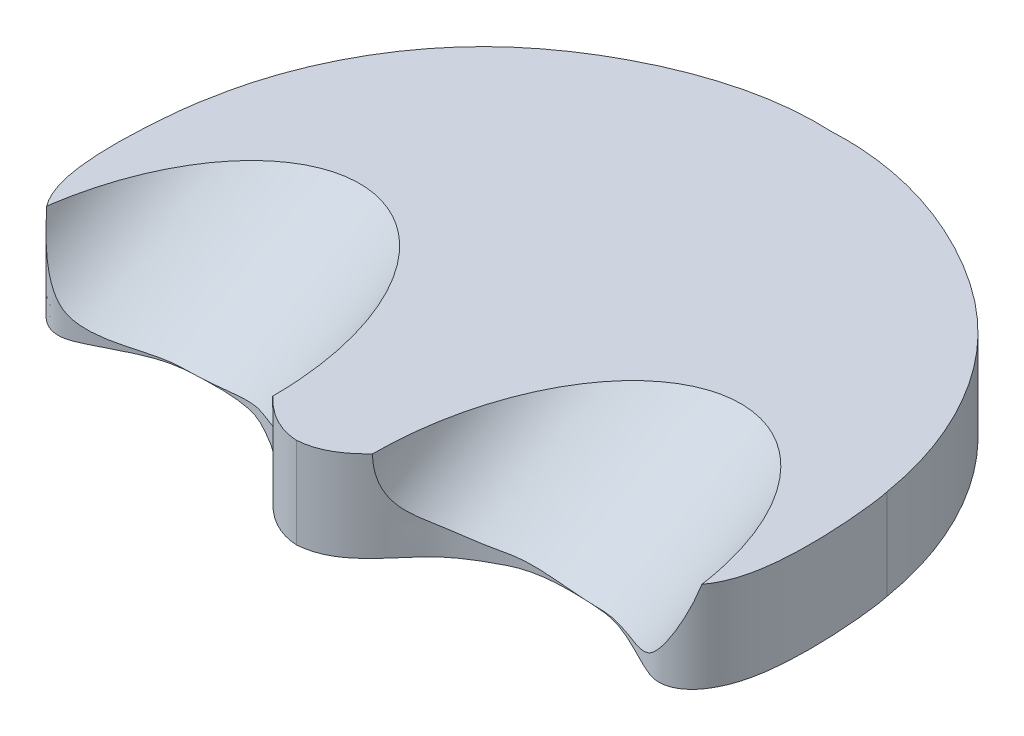
SolidWorks part; units mm, degrees
material "6061-T6 (SS)"
ref_plane "Front Plane" through (0, 0, 0) normal (0, 0, 1) x (1, 0, 0)
ref_plane "Top Plane" through (0, 0, 0) normal (0, 1, 0) x (1, 0, 0)
ref_plane "Right Plane" through (0, 0, 0) normal (1, 0, 0) x (0, 0, -1)
sketch "Sketch3" plane through (0, 0, 0) normal (0, 1, 0) x (1, 0, 0)
  line L0 (0, 0) -> (0, 159.1899) construction
  line L1 (0, 0) -> (0, -140.5301) construction
  line L2 (0, 0) -> (-190.5, 0) construction
  line L3 (0, 0) -> (190.5, 0) construction
  spline S0 degree 3 poles (-190.5, 0) (-184.3927, 37.537) (-157.2613, 93.9641) (-82.3875, 146.6227) (-31.3114, 160.7999) (0, 159.1899) knots 0 0 0 0 0.424401 0.65637 1 1 1 1
  spline S1 degree 3 poles (-190.5, 0) (-192.064, -4.9635) (-201.9672, -83.3146) (-174.6966, -109.29) (-151.6301, -100.568) (-131.4108, -87.7198) (-96.8436, -85.3754) (-78.6925, -86.2588) (-58.8335, -96.8794) (-37.3059, -109.9358) (-21.3496, -139.1148) (0, -140.5301) knots 0 0 0 0 0.166997 0.292321 0.319633 0.426735 0.458914 0.609242 0.64191 0.766802 1 1 1 1
  spline S2 degree 3 poles (190.5, 0) (192.064, -4.9635) (201.9672, -83.3146) (174.6966, -109.29) (151.6301, -100.568) (131.4108, -87.7198) (96.8436, -85.3754) (78.6925, -86.2588) (58.8335, -96.8794) (37.3059, -109.9358) (21.3496, -139.1148) (0, -140.5301) knots 0 0 0 0 0.166997 0.292321 0.319633 0.426735 0.458914 0.609242 0.64191 0.766802 1 1 1 1
  spline S3 degree 3 poles (190.5, 0) (184.3927, 37.537) (157.2613, 93.9641) (82.3875, 146.6227) (31.3114, 160.7999) (0, 159.1899) knots 0 0 0 0 0.424401 0.65637 1 1 1 1
  dimension "D1" = 381
  dimension "D2" = 299.72
  dimension "D3" = 159.1899
  dimension "D4" = 86.8953
  dimension "D5" = 104.4979
  dimension "D6" = 29.1616
  dimension "D7" = 92.2742
  dimension "D8" = 108.411
  dimension "D9" = 67.4883
  dimension "D10" = 43.7314
  dimension "D11" = 117.6915
  dimension "D12" = 162.2568
  dimension "D13" = 89.4522
  dimension "D14" = 140.1036
  dimension "D15" = 175.0666
  dimension "D16" = 50.2669
  dimension "D17" = 101.3666
  dimension "D18" = 138.1225
  dimension "D19" = 155.1557
  dimension "D20" = 192.0074
  dimension "D21" = 193.9268
  dimension "D23" = 76.6666
extrude "Boss-Extrude1" add sketch "Sketch3" along normal blind 50.8 from surface starting at plane "Top Plane"
sketch "Sketch5" plane through (0, 0, 0) normal (0, -1, 0) x (1, 0, 0)
  line L0 (0, 0) -> (0, -20.32) construction
  line L1 (31.75, -52.07) -> (-31.75, -52.07)
  line L2 (31.75, -52.07) -> (31.75, 11.43)
  line L3 (31.75, 11.43) -> (-31.75, 11.43)
  line L4 (-31.75, -52.07) -> (-31.75, 11.43)
  line L5 (31.75, -52.07) -> (-31.75, 11.43) construction
  line L6 (31.75, 11.43) -> (-31.75, -52.07) construction
  line L7 (-31.75, -52.07) -> (-31.75, -30.48)
  line L8 (-31.75, -30.48) -> (31.75, -30.48) construction
  line L9 (0, -20.32) -> (140.7253, -20.32) construction
  line L10 (0, -20.32) -> (0, -97.1287) construction
  line L11 (0, -20.32) -> (31.9753, -118.7297) construction
  line L13 (0, -20.32) -> (63.8443, -108.1942) construction
  line L14 (0, -20.32) -> (95.5392, -89.7333) construction
  line L15 (124.7166, -60.8429) -> (0, -20.32) construction
  line L16 (0, -20.32) -> (154.5508, 21.0918) construction
  line L17 (0, -20.32) -> (148.922, 65.6601) construction
  line L18 (0, -20.32) -> (-31.9753, -118.7297) construction
  line L19 (0, -20.32) -> (-63.8443, -108.1942) construction
  line L20 (0, -20.32) -> (-95.5392, -89.7333) construction
  line L21 (-124.7166, -60.8429) -> (0, -20.32) construction
  line L22 (0, -20.32) -> (-154.5508, 21.0918) construction
  line L23 (0, -20.32) -> (-148.922, 65.6601) construction
  spline S0 degree 3 poles (-148.922, 65.6601) (-157.8584, 40.2253) (-156.2837, 8.5854) (-143.1202, -28.9506) (-139.3242, -37.3463) (-130.3709, -53.1962) (-125.215, -60.649) (-118.0488, -69.1403) (-116.5795, -70.7975) (-113.5719, -74.0252) (-112.0368, -75.592) (-107.2801, -80.2116) (-103.9215, -83.1695) (-93.3361, -91.6595) (-85.5959, -96.8074) (-76.3408, -101.9556) (-75.3049, -102.5187) (-73.219, -103.6268) (-72.1677, -104.1726) (-69.0049, -105.7765) (-66.8862, -106.8006) (-60.5068, -109.7299) (-56.2231, -111.4921) (-47.6308, -114.6027) (-43.3223, -115.9511) (-34.7104, -118.209) (-30.4072, -119.1185) (-21.8242, -120.4791) (-17.5446, -120.9304) (-11.1443, -121.2499) (-9.0138, -121.2968) (-5.8216, -121.2757) (-4.1848, -121.2414) (-2.5489, -121.1705) (-1.9677, -121.1408) (-1.9605, -121.1404) (-1.2995, -121.1064) (-0.6497, -121.073) (0, -121.0396) knots -0.292878 -0.292878 -0.292878 -0.292878 0.125 0.125 0.25 0.25 0.375 0.375 0.40625 0.40625 0.4375 0.4375 0.5 0.5 0.625 0.625 0.640625 0.640625 0.65625 0.65625 0.6875 0.6875 0.75 0.75 0.8125 0.8125 0.875 0.875 0.9375 0.9375 0.96875 0.96875 0.984375 0.992798 0.992798 0.99292 0.99292 1 1 1 1
  spline S5 degree 3 poles (998.6789, -69.6893) (665.1581, -86.8384) (331.6156, -103.9885) (-1.9268, -121.1387) (-1.9605, -121.1404) (-1.9677, -121.1408) (-2.5489, -121.1705) (-4.1848, -121.2414) (-5.8216, -121.2757) (-9.0138, -121.2968) (-11.1443, -121.2499) (-17.5446, -120.9304) (-21.8242, -120.4791) (-30.4072, -119.1185) (-34.7104, -118.209) (-43.3223, -115.9511) (-47.6308, -114.6027) (-56.2231, -111.4921) (-60.5068, -109.7299) (-66.8862, -106.8006) (-69.0049, -105.7765) (-72.1677, -104.1726) (-73.219, -103.6268) (-75.3049, -102.5187) (-76.3408, -101.9556) (-85.5959, -96.8074) (-93.3361, -91.6595) (-103.9215, -83.1695) (-107.2801, -80.2116) (-112.0368, -75.592) (-113.5719, -74.0252) (-116.5795, -70.7975) (-118.0488, -69.1403) (-125.215, -60.649) (-130.3709, -53.1962) (-139.3242, -37.3463) (-143.1202, -28.9506) (-198.5095, 128.9933) (-22.362, 351.6373) (651.8169, -587.5188) knots -3.627409 -3.627409 -3.627409 -3.627409 0.006836 0.00708 0.00708 0.007202 0.007202 0.015625 0.03125 0.03125 0.0625 0.0625 0.125 0.125 0.1875 0.1875 0.25 0.25 0.3125 0.3125 0.34375 0.34375 0.359375 0.359375 0.375 0.375 0.5 0.5 0.5625 0.5625 0.59375 0.59375 0.625 0.625 0.75 0.75 0.875 0.875 3.034324 3.034324 3.034324 3.034324 only from (0, -121.0396) to (-152.8945, 6.1184)
  spline S6 degree 3 poles (-1687.8289, -2297.0686) (-150.4269, 537.0593) (218.9922, 187.4002) (143.1202, -28.9506) (139.3242, -37.3463) (130.3709, -53.1962) (125.215, -60.649) (118.0488, -69.1403) (116.5795, -70.7975) (113.5719, -74.0252) (112.0368, -75.592) (107.2801, -80.2116) (103.9215, -83.1695) (93.3361, -91.6595) (85.5959, -96.8074) (76.3408, -101.9556) (75.3049, -102.5187) (73.219, -103.6268) (72.1677, -104.1726) (69.0049, -105.7765) (66.8862, -106.8006) (60.5068, -109.7299) (56.2231, -111.4921) (47.6308, -114.6027) (43.3223, -115.9511) (34.7104, -118.209) (30.4072, -119.1185) (21.8242, -120.4791) (17.5446, -120.9304) (11.1443, -121.2499) (9.0138, -121.2968) (5.8216, -121.2757) (4.1848, -121.2414) (2.5489, -121.1705) (1.9677, -121.1408) (1.9605, -121.1404) (-997.3522, -69.7575) (-1996.6535, -18.3753) (-2996.029, 33.0152) knots -2.879056 -2.879056 -2.879056 -2.879056 0.125 0.125 0.25 0.25 0.375 0.375 0.40625 0.40625 0.4375 0.4375 0.5 0.5 0.625 0.625 0.640625 0.640625 0.65625 0.65625 0.6875 0.6875 0.75 0.75 0.8125 0.8125 0.875 0.875 0.9375 0.9375 0.96875 0.96875 0.984375 0.992798 0.992798 0.99292 0.99292 11.881939 11.881939 11.881939 11.881939 only from (152.8945, 6.1184) to (0, -121.0396)
  spline S8 degree 3 poles (148.922, 65.6601) (157.8584, 40.2253) (156.2837, 8.5854) (143.1202, -28.9506) (139.3242, -37.3463) (130.3709, -53.1962) (125.215, -60.649) (118.0488, -69.1403) (116.5795, -70.7975) (113.5719, -74.0252) (112.0368, -75.592) (107.2801, -80.2116) (103.9215, -83.1695) (93.3361, -91.6595) (85.5959, -96.8074) (76.3408, -101.9556) (75.3049, -102.5187) (73.219, -103.6268) (72.1677, -104.1726) (69.0049, -105.7765) (66.8862, -106.8006) (60.5068, -109.7299) (56.2231, -111.4921) (47.6308, -114.6027) (43.3223, -115.9511) (34.7104, -118.209) (30.4072, -119.1185) (21.8242, -120.4791) (17.5446, -120.9304) (11.1443, -121.2499) (9.0138, -121.2968) (5.8216, -121.2757) (4.1848, -121.2414) (2.5489, -121.1705) (1.9677, -121.1408) (1.9605, -121.1404) (1.2995, -121.1064) (0.6497, -121.073) (0, -121.0396) knots -0.292878 -0.292878 -0.292878 -0.292878 0.125 0.125 0.25 0.25 0.375 0.375 0.40625 0.40625 0.4375 0.4375 0.5 0.5 0.625 0.625 0.640625 0.640625 0.65625 0.65625 0.6875 0.6875 0.75 0.75 0.8125 0.8125 0.875 0.875 0.9375 0.9375 0.96875 0.96875 0.984375 0.992798 0.992798 0.99292 0.99292 1 1 1 1
  point P0 (0, -20.32)
  point P3 (0, -20.32)
  point P14 (0, 114.3)
  point P16 (0, 88.9)
  dimension "D1" = 20.32
  dimension "D2" = 63.5
  dimension "D3" = 63.5
  dimension "D4" = 21.59
  dimension "D6" = 25.4
  dimension "D7" = 88.9
  dimension "D8" = 18
  dimension "D9" = 18
  dimension "D10" = 18
  dimension "D11" = 18
  dimension "D12" = 15
  dimension "D13" = 15
  dimension "D5" = 38.1
sketch "Sketch7" plane through (0, 50.8, 0) normal (0, 1, 0) x (1, 0, 0)
  line L0 (-193.6723, -25.4) -> (193.6723, -25.4) construction
  spline S0 degree 3 poles (-190.5, 0) (-192.064, -4.9635) (-201.9672, -83.3146) (-174.6966, -109.29) (-151.6301, -100.568) (-131.4108, -87.7198) (-96.8436, -85.3754) (-78.6925, -86.2588) (-58.8335, -96.8794) (-37.3059, -109.9358) (-21.3496, -139.1148) (0, -140.5301) knots 0 0 0 0 0.166997 0.292321 0.319633 0.426735 0.458914 0.609242 0.64191 0.766802 1 1 1 1 construction
  spline S1 degree 3 poles (0, -140.5301) (21.3496, -139.1148) (37.3059, -109.9358) (58.8335, -96.8794) (78.6925, -86.2588) (96.8436, -85.3754) (131.4108, -87.7198) (151.6301, -100.568) (174.6966, -109.29) (201.9672, -83.3146) (192.064, -4.9635) (190.5, 0) knots 0 0 0 0 0.233198 0.35809 0.390758 0.541086 0.573265 0.680367 0.707679 0.833003 1 1 1 1 construction
  point P6 (0, 0)
  dimension "D1" = 25.4
ref_plane "Plane2" through (0, 1.7015, -2.947) normal (0, -0.5, 0.866) x (1, 0, 0)
sketch "Sketch6" plane through (0, 24.0865, 9.977) normal (0, 0.5, -0.866) x (-1, 0, 0)
  line L2 (0, 2.092) -> (0, -53.788) construction
  ellipse E0 centre (-106.8082, 81.0265) end of major axis (-185.6422, 81.0265) minor radius 63.7725
  ellipse E1 centre (106.8082, 81.0265) end of major axis (27.9741, 81.0265) minor radius 63.7725
  spline S3 degree 3 poles (0, 44.417) (-21.3496, 43.7094) (-37.3059, 29.1199) (-58.8335, 22.5917) (-78.6925, 17.2814) (-96.8436, 16.8397) (-131.4108, 18.0119) (-151.6301, 24.436) (-174.6966, 28.797) (-201.9672, 15.8093) (-192.064, -23.3663) (-190.5, -25.848) knots 0 0 0 0 0.233198 0.35809 0.390758 0.541086 0.573265 0.680367 0.707679 0.833003 1 1 1 1 construction
  spline S5 degree 3 poles (0, 88.4111) (-21.3496, 87.7035) (-37.3059, 73.114) (-58.8335, 66.5858) (-78.6925, 61.2755) (-96.8436, 60.8338) (-131.4108, 62.006) (-151.6301, 68.4301) (-174.6966, 72.7911) (-201.9672, 59.8034) (-192.064, 20.6278) (-190.5, 18.1461) knots 0 0 0 0 0.233198 0.35809 0.390758 0.541086 0.573265 0.680367 0.707679 0.833003 1 1 1 1 construction
  point P1 (-5.0467, -37.696)
  point P7 (0, 2.0303)
  point P8 (0, -25.848)
  point P52 (0, -25.848)
  dimension "D1" = 106.8745
  dimension "D2" = 106.8082
extrude "Cut-Extrude1" cut sketch "Sketch6" against normal through all and the other way through all
equation "\"Plate thickness\"=2"
equation "\"D1@Boss-Extrude1\"=\"Plate thickness\""
equation "\"Bracket Alignment\"= .80"
equation "\"D1@Sketch5\"=\"Bracket Alignment\""
